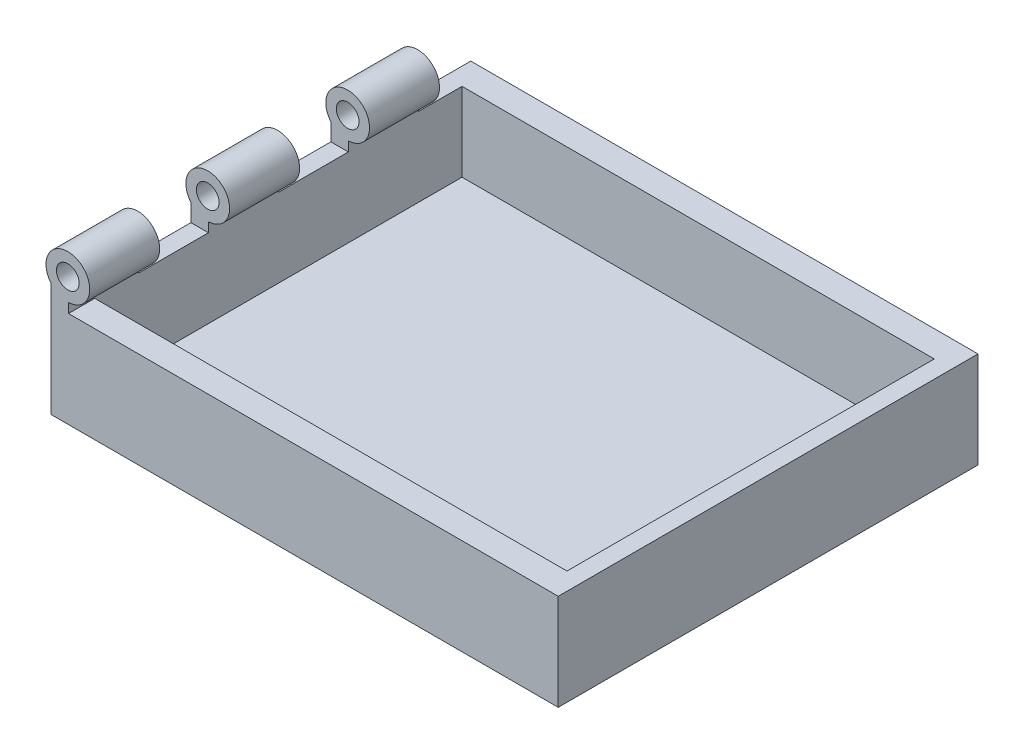
SolidWorks part; units mm, degrees
ref_plane "Front" through (0, 0, 0) normal (0, 0, 1) x (1, 0, 0)
ref_plane "Top" through (0, 0, 0) normal (0, 1, 0) x (1, 0, 0)
ref_plane "Right" through (0, 0, 0) normal (1, 0, 0) x (0, 0, -1)
sketch "Sketch1" plane through (0, 0, 0) normal (0, 1, 0) x (1, 0, 0)
  line L1 (-36.83, 30.48) -> (36.83, 30.48)
  line L2 (-36.83, 30.48) -> (-36.83, -30.48)
  line L3 (-36.83, -30.48) -> (36.83, -30.48)
  line L4 (36.83, 30.48) -> (36.83, -30.48)
  line L5 (-36.83, 30.48) -> (36.83, -30.48) construction
  line L6 (-36.83, -30.48) -> (36.83, 30.48) construction
  line L7 (-34.29, 26.67) -> (34.29, 26.67)
  line L8 (-34.29, 26.67) -> (-34.29, -26.67)
  line L9 (-34.29, -26.67) -> (34.29, -26.67)
  line L10 (34.29, 26.67) -> (34.29, -26.67)
  line L11 (-34.29, 26.67) -> (34.29, -26.67) construction
  line L12 (-34.29, -26.67) -> (34.29, 26.67) construction
  point P0 (0, 0)
  point P6 (0, 0)
  dimension "D1" = 60.96
  dimension "D2" = 73.66
  dimension "D3" = 53.34
  dimension "D4" = 68.58
extrude "pcb-base" add sketch "Sketch1" along normal blind 2.54 contours L8 L7 L10 L9
extrude "pcb-wall" add sketch "Sketch1<4>" along normal blind 13.97
sketch "Sketch1<4>" plane through (0, 0, 0) normal (0, 1, 0) x (1, 0, 0) same geometry as "Sketch1"
sketch "Sketch3" plane through (-36.83, 0, 0) normal (-1, 0, 0) x (0, 0, 1)
  line L0 (-30.48, 13.97) -> (-30.48, 0) construction
  line L1 (-30.48, 13.97) -> (30.48, 13.97) construction
  circle A0 centre (20.32, 4.318) radius 1.651
  dimension "D2" = 9.652
  dimension "D3" = 3.302
  dimension "D1" = 50.8
extrude "battery-gap" cut sketch "Sketch3" against normal up to vertex (2.54 mm away) contours A0 up to point (-34.29, 13.97, 26.67)
sketch "Sketch5" plane through (0, 0, 30.48) normal (0, 0, 1) x (1, 0, 0)
  line L0 (-34.29, 13.97) -> (-34.29, 2.54) construction
  line L2 (-36.83, 13.97) -> (-34.29, 13.97)
  line L3 (-36.83, 13.97) -> (-36.83, 16.51)
  line L4 (-36.83, 16.51) -> (-34.29, 16.51)
  line L5 (-34.29, 13.97) -> (-34.29, 16.51)
  circle A0 centre (-34.3884, 18.5396) radius 3.175
  circle A2 centre (-34.3884, 18.5396) radius 1.651
  point P9 (-34.29, 19.8339)
  line M4 (36.83, 13.97) -> (-36.83, 13.97)
  dimension "D1" = 6.35
  dimension "D2" = 1.524
  dimension "D3" = 2.54
  dimension "D4" = 2.032
extrude "pcb-hinge" add sketch "Sketch5" against normal blind 10.16 contours A0 L3 L5 M4 | L4 A0 L5 | L5 A0 L4 A2 region at (-35.6926, 14.8665, 30.48) region at (-35.4369, 21.4412, 30.48) region at (-35.2766, 16.0381, 30.48)
pattern_linear "LPattern2" count 3 spacing 20.32 along (0, 0, -1) of "pcb-hinge"
